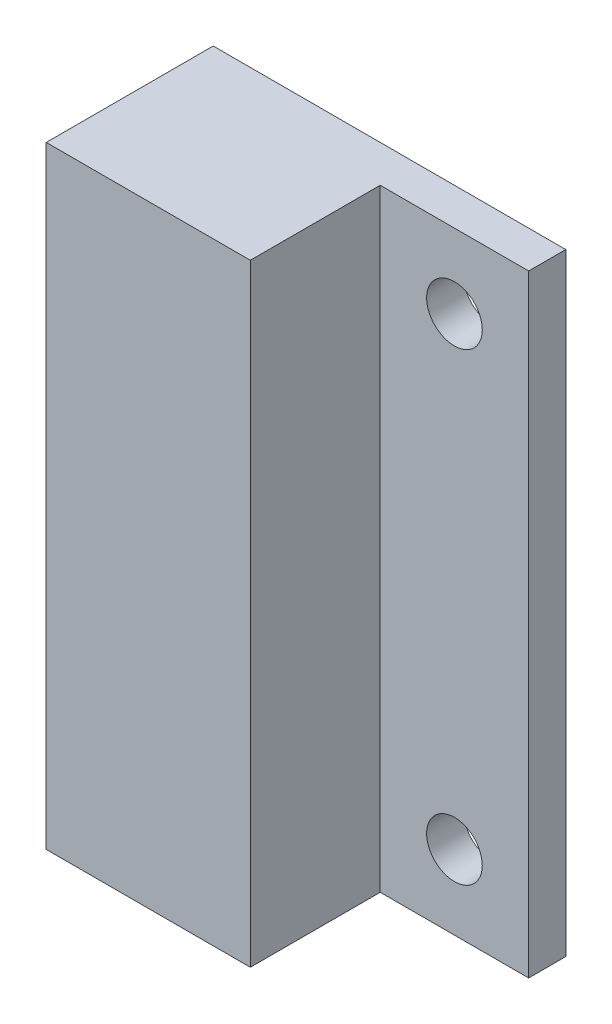
SolidWorks part; units mm, degrees
ref_plane "Front Plane" through (0, 0, 0) normal (0, 0, 1) x (1, 0, 0)
ref_plane "Top Plane" through (0, 0, 0) normal (0, 1, 0) x (1, 0, 0)
ref_plane "Right Plane" through (0, 0, 0) normal (1, 0, 0) x (0, 0, -1)
sketch "Sketch1" plane through (0, 0, 0) normal (0, 0, 1) x (1, 0, 0)
  line L1 (0, 0) -> (19, 0)
  line L2 (0, 0) -> (0, 33)
  line L3 (0, 33) -> (19, 33)
  line L4 (19, 0) -> (19, 33)
  dimension "D1" = 33
  dimension "D2" = 19
extrude "Boss-Extrude1" add sketch "Sketch1" along normal blind 9
sketch "Sketch3" plane through (0, 0, 9) normal (0, 0, 1) x (1, 0, 0)
  line L0 (0, 0) -> (19, 0) construction
  line L1 (19, 33) -> (11, 33)
  line L2 (19, 33) -> (19, 0)
  line L3 (19, 0) -> (11, 0)
  line L4 (11, 33) -> (11, 0)
  dimension "D1" = 8
extrude "Cut-Extrude1" cut sketch "Sketch3" against normal blind 7
ref_plane "Plane1" through (0, 16.5, 0) normal (0, -1, 0) x (-1, 0, 0)
ref_plane "Plane2" through (15, 0, 0) normal (1, 0, 0) x (0, 0, -1)
hole_wizard "Ø3.0mm Dowel Hole1" positions "Sketch6" profile "Sketch7" hole size "Ø3.0" standard "ANSI Metric" end condition up to next
sketch "Sketch6" plane through (0, 0, 2) normal (0, 0, 1) x (1, 0, 0)
  line L0 (15, 29) -> (15, 4) construction
  line L2 (-4.95, 16.5) -> (4.95, 16.5) construction
  line L3 (15, -4.95) -> (15, 4.95) construction
  point P0 (15, 4)
  point P2 (15, 29)
  point P10 (15, 16.5)
  dimension "D1" = 25
sketch "Sketch7" plane through (15, 4, 2) normal (1, 0, 0) x (0, -1, 0)
  line L0 (0, 0) -> (0, 2)
  line L1 (0, 2) -> (1.5, 2)
  line L2 (1.5, 2) -> (1.5, 0)
  line L5 (1.5, 0) -> (0, 0)
  line L11 (0, -6.35) -> (0, 107.95) construction
  dimension "Thru Hole Dia." = 3
  dimension "Thru Hole Depth" = 2
